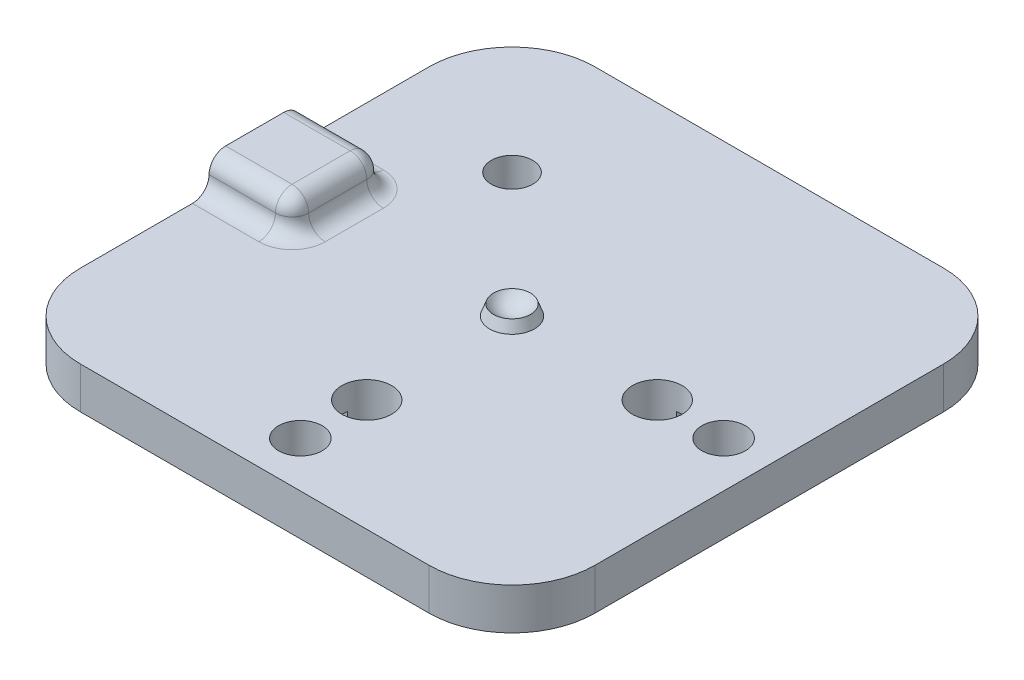
SolidWorks part; units mm, degrees
material "ABS"
ref_plane "Front Plane" through (0, 0, 0) normal (0, 0, 1) x (1, 0, 0)
ref_plane "Top Plane" through (0, 0, 0) normal (0, 1, 0) x (1, 0, 0)
ref_plane "Right Plane" through (0, 0, 0) normal (1, 0, 0) x (0, 0, -1)
sketch "Sketch3" plane through (0, 0, 0) normal (0, 0, 1) x (1, 0, 0)
  line L3 (0, 0) -> (2.7, 0)
  line L4 (0, 0) -> (0, 2.8) construction
  line L5 (2.2332, 1.2825) -> (2.7, 0)
  line L6 (0, 0.1) -> (0, 0)
  arc A1 (0, 0.1) -> (2.2332, 1.2825) centre (0, 2.8) ccw
  dimension "D2" = 2.7
  dimension "D1" = 0.1
  dimension "D4" = 2.7
  dimension "D3" = 70
revolve "Revolve1" add sketch "Sketch3" angle 360 about L6
sketch "Sketch4" plane through (0, 0, 0) normal (0, -1, 0) x (1, 0, 0)
  line L0 (0, 0) -> (-31, 0) construction
  line L1 (-31, -31) -> (31, -31)
  line L2 (-31, -31) -> (-31, 31)
  line L3 (-31, 31) -> (31, 31)
  line L4 (31, -31) -> (31, 31)
  line L5 (-31, -31) -> (31, 31) construction
  line L6 (-31, 31) -> (31, -31) construction
  line L7 (0, 17.5) -> (0, 0) construction
  line L8 (0, 0) -> (17.5, 0) construction
  line L9 (0, 0) -> (0, 31) construction
  line L10 (-15, -15) -> (0, -15) construction
  line L11 (-15, -15) -> (-15, 0) construction
  circle A0 centre (17.5, 0) radius 3
  circle A1 centre (0, 17.5) radius 3
  circle A2 centre (-15, -15) radius 2.5
  circle A3 centre (0, 25.5) radius 2.625
  circle A4 centre (25.5, 0) radius 2.625
  point P0 (0, 0)
  dimension "D3" = 6
  dimension "D4" = 5
  dimension "D6" = 5.25
  dimension "D1" = 31
  dimension "D2" = 17.5
  dimension "D5" = 15
  dimension "D7" = 8
  dimension "D8" = 8
extrude "Boss-Extrude2" add sketch "Sketch4" along normal blind 5
sketch "Sketch5" plane through (0, -5, 0) normal (0, -1, 0) x (1, 0, 0)
  line L0 (-5.2, 18.1) -> (5.2, 18.1)
  line L1 (5.2, 18.1) -> (5.2, 16.9)
  line L2 (5.2, 16.9) -> (-5.2, 16.9)
  line L3 (-5.2, 16.9) -> (-5.2, 18.1)
  line L4 (16.9, 5.2) -> (18.1, 5.2)
  line L5 (18.1, 5.2) -> (18.1, -5.2)
  line L6 (18.1, -5.2) -> (16.9, -5.2)
  line L7 (16.9, -5.2) -> (16.9, 5.2)
  line L8 (-18.2527, -10.8988) -> (-10.8988, -18.2527)
  line L9 (-10.8988, -18.2527) -> (-11.7473, -19.1012)
  line L10 (-11.7473, -19.1012) -> (-19.1012, -11.7473)
  line L11 (-19.1012, -11.7473) -> (-18.2527, -10.8988)
  line L12 (-15, -15) -> (-15.4243, -15.4243) construction
  line L13 (-15, -15) -> (-14.5757, -14.5757) construction
  line L14 (-15, -15) -> (-18.677, -11.323) construction
  line L15 (-15, -15) -> (-11.323, -18.677) construction
  line L16 (-31, 31) -> (-31, -31) construction
  point P0 (0, 17.5)
  point P1 (17.5, 0)
  point P3 (-15, -15)
  point P16 (5.2, 17.5)
  point P19 (-5.2, 17.5)
  point P20 (0, 18.1)
  point P21 (0, 16.9)
  point P22 (16.9, 0)
  point P23 (18.1, 0)
  point P24 (17.5, 5.2)
  point P25 (17.5, -5.2)
  dimension "D1" = 10.4
  dimension "D2" = 1.2
  dimension "D3" = 135
extrude "Cut-Extrude1" cut sketch "Sketch5" against normal blind 2
sketch "Contour for hex bolt precision screws - 2.1 mm cut extrude" [suppressed] plane through (0, 0, 0) normal (0, 1, 0) x (1, 0, 0)
  line L0 (31, -31) -> (-31, -31) construction
  line L1 (1.8475, -22.3) -> (-1.8475, -22.3)
  line L2 (-1.8475, -22.3) -> (-3.695, -25.5)
  line L3 (-3.695, -25.5) -> (-1.8475, -28.7)
  line L4 (-1.8475, -28.7) -> (1.8475, -28.7)
  line L5 (1.8475, -28.7) -> (3.695, -25.5)
  line L6 (3.695, -25.5) -> (1.8475, -22.3)
  line L7 (28.7, 1.8475) -> (25.5, 3.695)
  line L8 (25.5, 3.695) -> (22.3, 1.8475)
  line L9 (22.3, 1.8475) -> (22.3, -1.8475)
  line L10 (22.3, -1.8475) -> (25.5, -3.695)
  line L11 (25.5, -3.695) -> (28.7, -1.8475)
  line L12 (28.7, -1.8475) -> (28.7, 1.8475)
  line L13 (31, 31) -> (31, -31) construction
  circle A0 centre (0, -25.5) radius 3.2 construction
  circle A1 centre (25.5, 0) radius 3.2 construction
  dimension "D1" = 6.4
fillet "Fillet1" radius 10 4 edges at (-31, -2.5, -31) (31, -2.5, -31) (-31, -2.5, 31) (31, -2.5, 31)
sketch "Sketch6" plane through (0, 0, 0) normal (0, 1, 0) x (1, 0, 0)
  line L0 (-31, 5.5) -> (-21, 5.5)
  line L1 (-31, -21) -> (-31, 21) construction
  line L2 (-21, 5.5) -> (-21, -5.5)
  line L3 (-21, -5.5) -> (-31, -5.5)
  line L4 (-31, -5.5) -> (-31, 5.5)
  point P4 (-31, 0)
  point P7 (-21, 0)
  dimension "D1" = 11
  dimension "D2" = 10
extrude "Boss-Extrude3" add sketch "Sketch6" along normal blind 4
sketch "Sketch7" plane through (-31, 0, 0) normal (-1, 0, 0) x (0, 0, 1)
  line L0 (-5.5, 4) -> (5.5, 4) construction
  circle A0 centre (0, -0.5) radius 2.6
  point P4 (0, 4)
  dimension "D2" = 5.2
  dimension "D1" = 4.5
extrude "Cut-Extrude2" cut sketch "Sketch7" against normal blind 9
chamfer "Chamfer1" distance 1 angle 45 1 edges at (-31, -0.5, 2.6)
fillet "Fillet2" radius 2 6 edges at (-21, 4, 0) (-21, 0, 0) (-26, 4, -5.5) (-26, 0, -5.5) (-26, 4, 5.5) (-26, 0, 5.5)
